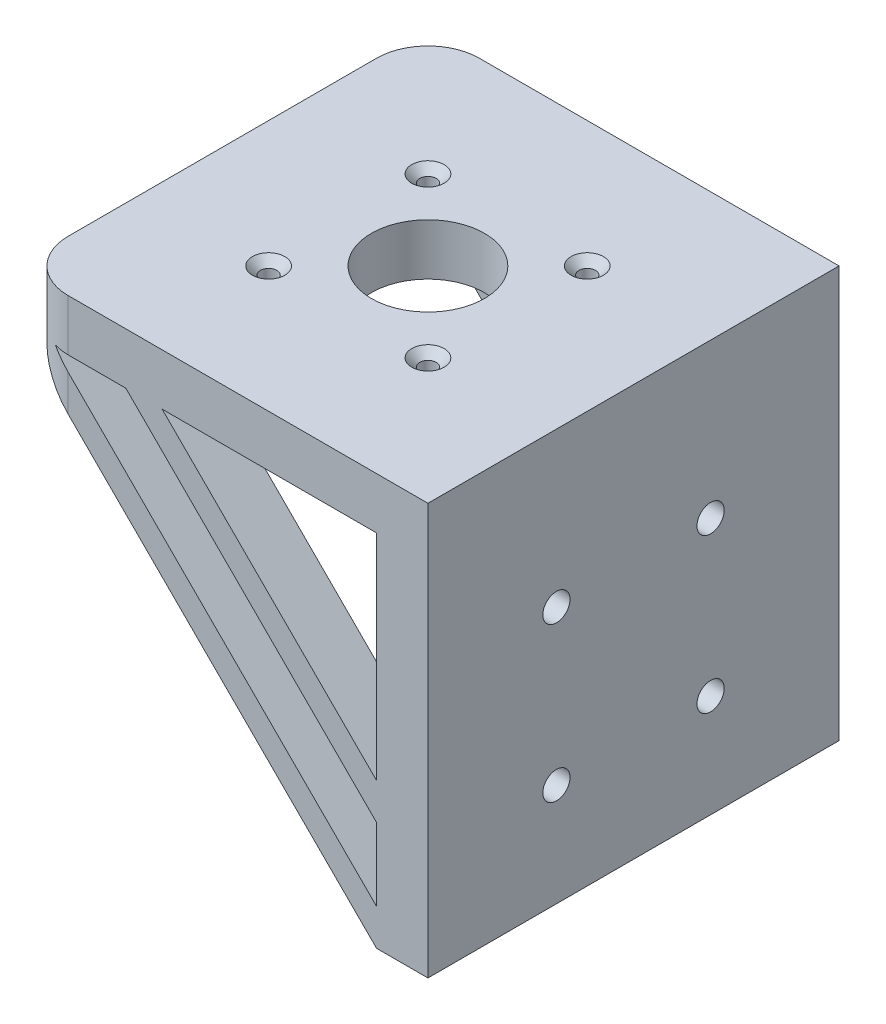
SolidWorks part; units mm, degrees
ref_plane "Front Plane" through (0, 0, 0) normal (0, 0, 1) x (1, 0, 0)
ref_plane "Top Plane" through (0, 0, 0) normal (0, 1, 0) x (1, 0, 0)
ref_plane "Right Plane" through (0, 0, 0) normal (1, 0, 0) x (0, 0, -1)
sketch "Sketch1" plane through (0, 0, 0) normal (0, 1, 0) x (1, 0, 0)
  line L1 (-40, -40) -> (40, -40)
  line L2 (-40, -40) -> (-40, 40)
  line L3 (-40, 40) -> (40, 40)
  line L4 (40, -40) -> (40, 40)
  line L5 (-40, -40) -> (40, 40) construction
  line L6 (-40, 40) -> (40, -40) construction
  circle A0 centre (0, 0) radius 11
  point P0 (0, 0)
  dimension "D3" = 22
  dimension "D1" = 80
  dimension "D2" = 80
extrude "Boss-Extrude1" add sketch "Sketch1" along normal blind 10
sketch "Sketch2" plane through (0, 10, 0) normal (0, 1, 0) x (1, 0, 0)
  line L1 (-15.5, -15.5) -> (15.5, -15.5)
  line L2 (-15.5, -15.5) -> (-15.5, 15.5)
  line L3 (-15.5, 15.5) -> (15.5, 15.5)
  line L4 (15.5, -15.5) -> (15.5, 15.5)
  line L5 (-15.5, -15.5) -> (15.5, 15.5) construction
  line L6 (-15.5, 15.5) -> (15.5, -15.5) construction
  point P0 (0, 0)
  dimension "D1" = 31
  dimension "D2" = 31
hole_wizard "CSK for M3 Countersunk Flat Head Screw1" positions "Sketch3" profile "Sketch4" countersink size "M3" standard "ISO" end condition through all
sketch "Sketch3" plane through (0, 10, 0) normal (0, 1, 0) x (1, 0, 0)
  point P0 (-15.5, 15.5)
  point P3 (15.5, 15.5)
  point P6 (15.5, -15.5)
  point P9 (-15.5, -15.5)
sketch "Sketch4" plane through (-15.5, 10, -15.5) normal (1, 0, 0) x (0, 0, 1)
  line L0 (0, 0) -> (0, 10)
  line L1 (0, 10) -> (1.6, 10)
  line L2 (1.6, 10) -> (1.6, 1.55)
  line L3 (1.6, 1.55) -> (3.15, 0)
  line L5 (3.15, 0) -> (0, 0)
  line L6 (-1.6, 1.55) -> (-3.15, 0) construction
  line L11 (0, -6.35) -> (0, 107.95) construction
  dimension "Thru Hole Dia." = 3.2
  dimension "Thru Hole Depth" = 10
  dimension "Near C'Sink Dia." = 6.3
  dimension "Near C'Sink Angle" = 90
sketch "Sketch5" plane through (0, 0, 0) normal (0, -1, 0) x (-1, 0, 0)
  line L0 (-40, 40) -> (40, 40) construction
  line L1 (-40, -40) -> (-30, -40)
  line L2 (-40, -40) -> (-40, 40)
  line L3 (-40, 40) -> (-30, 40)
  line L4 (-30, -40) -> (-30, 40)
  dimension "D1" = 10
extrude "Boss-Extrude2" add sketch "Sketch5" along normal blind 70
sketch "Sketch6" plane through (0, 0, 40) normal (0, 0, 1) x (1, 0, 0)
  line L0 (-40, 0) -> (30, -70)
  line L1 (-11.7157, 0) -> (30, -41.7157)
  line L2 (-40, 0) -> (30, 0) construction
  line L3 (30, -70) -> (30, 0) construction
  line L4 (-15.2513, -3.5355) -> (26.4645, -45.2513)
  line L5 (26.4645, -45.2513) -> (30, -48.7868)
  line L6 (-15.2513, -3.5355) -> (-18.7868, 0)
  line L7 (-36.4645, 3.5355) -> (33.5355, -66.4645)
  line L14 (-40, 0) -> (30, 0)
  line L15 (30, 0) -> (30, -70)
  line L16 (30, -70) -> (40, -70)
  line L17 (40, -70) -> (40, 10)
  line L18 (40, 10) -> (-40, 10)
  line L19 (-40, 10) -> (-40, 0)
  line L20 (-40, 0) -> (30, 0)
  line L21 (30, 0) -> (30, -70)
  line L22 (30, -70) -> (40, -70)
  line L23 (40, -70) -> (40, 10)
  line L24 (40, 10) -> (-40, 10)
  line L25 (-40, 10) -> (-40, 0)
  line M12 (-40, 0) -> (30, 0)
  line M13 (30, 0) -> (30, -70)
  dimension "D1" = 20
  dimension "D2" = 5
  dimension "D3" = 5
  dimension "D4" = 0
extrude "Boss-Extrude3" add sketch "Sketch6" against normal blind 10 contours L6 L4 L5 L1 M13 M12 | L7 L0 M12 M13 region at (-3.2636, -33.2636, 40) region at (7.3283, -22.6717, 40)
ref_plane "Plane2" through (0, 0, 0) normal (0, 0, 1) x (1, 0, 0)
mirror "Mirror1" about plane through (0, 0, 0) normal (0, 0, 1) of "Boss-Extrude3"
sketch "Sketch7" plane through (30, 0, 0) normal (-1, 0, 0) x (0, 0, 1)
  line L0 (30, -70) -> (-30, -70) construction
  line L1 (15, -20) -> (-15, -20)
  line L2 (15, -20) -> (15, -50)
  line L3 (15, -50) -> (-15, -50)
  line L4 (-15, -20) -> (-15, -50)
  line L5 (15, -20) -> (-15, -50) construction
  line L6 (15, -50) -> (-15, -20) construction
  point P0 (0, -35)
  dimension "D1" = 35
  dimension "D2" = 30
  dimension "D3" = 30
hole_wizard "CSK for M5 Countersunk Flat Head Screw1" positions "Sketch8" profile "Sketch9" countersink size "M5" standard "ISO" end condition through all
sketch "Sketch8" plane through (30, 0, 0) normal (-1, 0, 0) x (0, 0, 1)
  point P0 (15, -20)
  point P3 (15, -50)
  point P6 (-15, -50)
  point P9 (-15, -20)
sketch "Sketch9" plane through (30, -20, 15) normal (0, 1, 0) x (0, 0, 1)
  line L0 (0, 0) -> (0, 10)
  line L1 (0, 10) -> (2.65, 10)
  line L2 (2.65, 10) -> (2.65, 2.55)
  line L3 (2.65, 2.55) -> (5.2, 0)
  line L5 (5.2, 0) -> (0, 0)
  line L6 (-2.65, 2.55) -> (-5.2, 0) construction
  line L11 (0, -6.35) -> (0, 107.95) construction
  dimension "Thru Hole Dia." = 5.3
  dimension "Thru Hole Depth" = 10
  dimension "Near C'Sink Dia." = 10.4
  dimension "Near C'Sink Angle" = 90
fillet "Fillet1" radius 10 2 edges at (-40, 5, -40) (-40, 5, 40)
